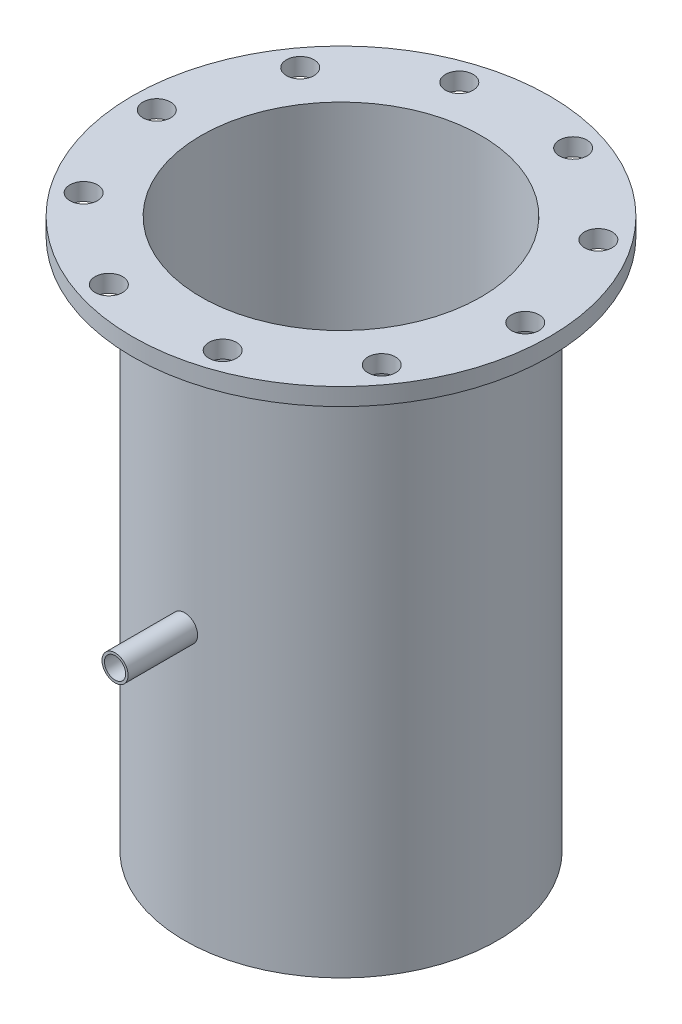
SolidWorks part; units mm, degrees
other "DetailItem1"
other "DetailItem2"
other "Weld Folder"
other "Weld Bead1"
other "Weld Bead2"
material "1023 Carbon Steel Sheet (SS)"
ref_plane "Front Plane" through (0, 0, 0) normal (0, 0, 1) x (1, 0, 0)
ref_plane "Top Plane" through (0, 0, 0) normal (0, 1, 0) x (1, 0, 0)
ref_plane "Right Plane" through (0, 0, 0) normal (1, 0, 0) x (0, 0, -1)
sketch "Sketch1" plane through (0, 0, 0) normal (0, 0, 1) x (1, 0, 0)
  line L0 (0, 0) -> (0, -134.8652) construction
  line L1 (51.1302, 0) -> (51.1302, -179.4164)
  line L2 (51.1302, -200.6) -> (57.15, -200.6)
  line L3 (57.15, -200.6) -> (57.15, -8.89)
  line L4 (54.61, -6.35) -> (76.2, -6.35)
  line L5 (76.2, -6.35) -> (76.2, 0)
  line L6 (76.2, 0) -> (51.1302, 0)
  line L7 (51.1302, -188.027) -> (53.848, -188.027)
  line L8 (53.848, -188.027) -> (53.848, -191.075)
  line L9 (53.848, -191.075) -> (51.1302, -191.075)
  line L10 (51.1302, -184.217) -> (53.6194, -184.217)
  line L11 (51.1302, -191.075) -> (51.1302, -200.6)
  line L12 (57.15, -8.89) -> (54.61, -6.35)
  line L13 (53.6194, -184.217) -> (53.6194, -179.4164)
  line L14 (53.6194, -179.4164) -> (51.1302, -179.4164)
  line L15 (-56.1848, -191.075) -> (56.1848, -191.075) construction
  line L16 (-50.1022, -191.075) -> (50.1022, -191.075) construction
  line L17 (51.1302, -184.217) -> (51.1302, -188.027)
  dimension "D1" = 51.1302
  dimension "D2" = 57.15
  dimension "D3" = 76.2
  dimension "D4" = 6.35
  dimension "D5" = 9.525
  dimension "D6" = 53.848
  dimension "D7" = 3.048
  dimension "D8" = 3.81
  dimension "D9" = 45
  dimension "D10" = 2.54
  dimension "D11" = 4.8006
  dimension "D12" = 53.6194
revolve "Revolve1" add sketch "Sketch1" angle 360 about L0
hole_wizard "Tap Drill for 3/8-16 Tap1" positions "Sketch2" profile "Sketch3" hole size "3/8" standard "ANSI Inch" end condition through all
sketch "Sketch2" plane through (0, 0, 0) normal (0, 1, 0) x (1, 0, 0)
  point P1 (67.31, 0)
  dimension "D1" = 67.31
sketch "Sketch3" plane through (67.31, 0, 0) normal (1, 0, 0) x (0, 0, 1)
  line L0 (0, 0) -> (0, 200.6)
  line L1 (0, 200.6) -> (5.0419, 200.6)
  line L2 (5.0419, 200.6) -> (5.0419, 0)
  line L5 (5.0419, 0) -> (0, 0)
  line L11 (0, -6.35) -> (0, 107.95) construction
  dimension "Thru Hole Dia." = 10.0838
  dimension "Thru Hole Depth" = 200.6
pattern_circular "CirPattern1" count 10 over 360 about axis through (0, 0, 0) along (0, 1, 0) of "Tap Drill for 3/8-16 Tap1"
ref_plane "Plane1" through (0, 0, 57.15) normal (0, 0, 1) x (1, 0, 0)
sketch "Sketch4" plane through (0, 0, 57.15) normal (0, 0, 1) x (1, 0, 0)
  circle A0 centre (0, -101.6) radius 4.7625
  circle A1 centre (0, -101.6) radius 3.8735
  dimension "D1" = 9.525
  dimension "D2" = 0.889
  dimension "D3" = 101.6
extrude "Boss-Extrude1" add sketch "Sketch4" along normal blind 25.4 separate body
hole_wizard "1/8 (0.125) Diameter Hole3" positions "3DSketch2" profile "Sketch11" hole size "1/8" standard "ANSI Inch"
sketch3d "3DSketch2"
  circle A0 centre (0, -101.6, 57.15) radius 4.1349 construction
  circle A1 centre (0, -101.6, 57.15) radius 4.7625 construction
  point P6 (0, -101.6, 61.2849)
  point P19 (0, -101.6, 61.9125)
  point P21 (0, -101.6, 57.15)
sketch "Sketch11" plane through (0, -101.6, 57.15) normal (1, 0, 0) x (0, -1, 0)
  line L0 (0, 0) -> (0, 26.3539)
  line L1 (0, 26.3539) -> (1.5875, 25.4)
  line L2 (1.5875, 25.4) -> (1.5875, 0)
  line L5 (1.5875, 0) -> (0, 0)
  line L10 (0, 26.3539) -> (-1.5875, 25.4) construction
  line L11 (0, -6.35) -> (0, 107.95) construction
  dimension "Hole Dia." = 3.175
  dimension "Hole Depth" = 25.4
  dimension "Drill Angle" = 118
